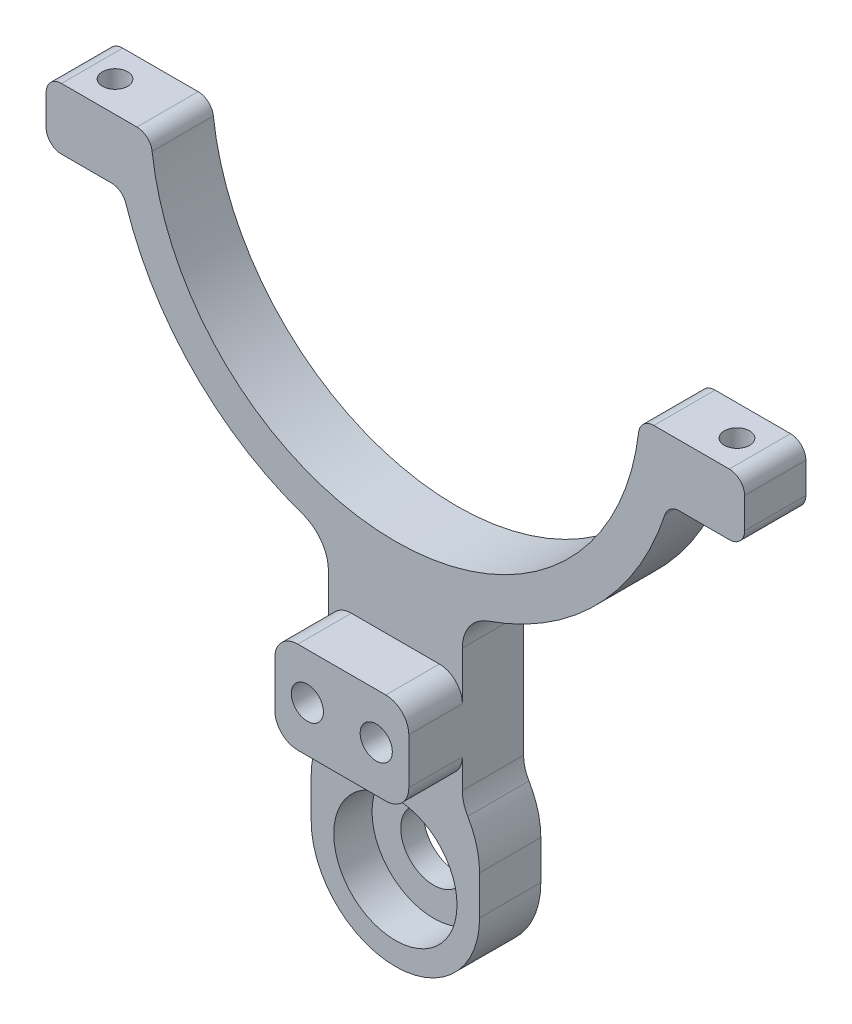
SolidWorks part; units mm, degrees
ref_plane "Front Plane" through (0, 0, 0) normal (0, 0, 1) x (1, 0, 0)
ref_plane "Top Plane" through (0, 0, 0) normal (0, 1, 0) x (1, 0, 0)
ref_plane "Right Plane" through (0, 0, 0) normal (1, 0, 0) x (0, 0, -1)
sketch "Sketch2" plane through (0, 0, 0) normal (0, 0, 1) x (1, 0, 0)
  circle A0 centre (0, 0) radius 31.7 construction
  dimension "D1" = 63.4
sketch "Sketch3" plane through (0, 0, 0) normal (0, 0, 1) x (1, 0, 0)
  line L0 (-31.9374, -2) -> (-45.623, -2)
  line L1 (31.9374, -2) -> (45.623, -2)
  line L7 (-11, -35.327) -> (-11, -80.1)
  line L8 (-11, -80.1) -> (11, -80.1)
  line L9 (11, -80.1) -> (11, -35.327)
  line L11 (35.623, -10) -> (45.623, -10)
  line L12 (45.623, -10) -> (45.623, -2)
  line L13 (-35.623, -10) -> (-45.623, -10)
  line L14 (-45.623, -10) -> (-45.623, -2)
  line L15 (40.623, -10) -> (40.623, -2) construction
  line L16 (37.623, -6) -> (43.623, -6) construction
  circle A1 centre (0, -69.1) radius 4 construction
  arc A2 (31.9374, -2) -> (-31.9374, -2) centre (0, 0) cw
  circle A3 centre (0, 0) radius 31.7 construction
  circle A7 centre (0, -69.1) radius 8.05
  arc A8 (11, -35.327) -> (35.623, -10) centre (0, 0) ccw
  arc A9 (-11, -35.327) -> (-35.623, -10) centre (0, 0) cw
  point P9 (0, -80.1)
  point P24 (40.623, -6)
  dimension "D1" = 0.3
  dimension "D3" = 37.4
  dimension "D4" = 8
  dimension "D5" = 16.1
  dimension "D7" = 5
  dimension "D2" = 48.4
  dimension "D6" = 22
  dimension "D8" = 8
  dimension "D9" = 6
  dimension "D10" = 2
  dimension "D11" = 2
  dimension "D12" = 2
extrude "Boss-Extrude1" add sketch "Sketch3" along normal blind 8
sketch "Sketch4" plane through (0, 0, 0) normal (0, 0, 1) x (1, 0, 0)
  circle A0 centre (0, -69.1) radius 8.05 construction
  circle A1 centre (0, -69.1) radius 8.05
  circle A2 centre (0, -69.1) radius 4.3
  dimension "D1" = 8.6
extrude "Boss-Extrude2" add sketch "Sketch4" along normal offset from surface (3 mm away) 5 up to face at (0, -26.2592, 8)
chamfer "Chamfer1" distance 3 angle 45 1 edges at (0, -80.1, 0)
fillet "Fillet1" radius 11 2 edges at (-11, -80.1, 5.5) (11, -80.1, 5.5)
sketch "Sketch5" plane through (0, -10, 0) normal (0, -1, 0) x (1, 0, 0)
  line L0 (37.623, 0) -> (43.623, 0) construction
  line L1 (37.623, 0) -> (43.623, 0) construction
  line L2 (40.623, 0) -> (40.623, 8) construction
  line L3 (45.623, 8) -> (31.9374, 8) construction
  line L4 (0, 0) -> (0, 8) construction
  line L5 (31.7, 0) -> (-31.7, 0) construction
  line L6 (31.9374, 8) -> (-31.9374, 8) construction
  circle A0 centre (40.623, 4) radius 1.65
  dimension "D1" = 3.3
extrude "Cut-Extrude1" cut sketch "Sketch5" against normal through all
sketch "Sketch6" plane through (0, -10, 0) normal (0, -1, 0) x (1, 0, 0)
  circle A0 centre (40.623, 4) radius 3
  dimension "D1" = 6
extrude "Cut-Extrude2" cut sketch "Sketch6" against normal blind 3
mirror "Mirror1" about plane through (0, 0, 0) normal (1, 0, 0) of "Cut-Extrude2", "Cut-Extrude1"
sketch "Sketch7" plane through (0, 0, 8) normal (0, 0, 1) x (1, 0, 0)
  line L0 (-4.5, -49) -> (4.5, -49) construction
  circle A0 centre (-4.5, -49) radius 2.1
  circle A1 centre (4.5, -49) radius 2.1
  point P4 (0, -49)
  dimension "D2" = 4.2
  dimension "D1" = 9
  dimension "D3" = 49
extrude "Cut-Extrude3" cut sketch "Sketch7" against normal blind 5
sketch "Sketch8" plane through (0, 0, 8) normal (0, 0, 1) x (1, 0, 0)
  circle A0 centre (4.5, -49) radius 2.1 construction
  circle A1 centre (-4.5, -49) radius 2.1 construction
  circle A2 centre (4.5, -49) radius 2.1 construction
  circle A3 centre (-4.5, -49) radius 2.1 construction
  circle A4 centre (4.5, -49) radius 1.65
  circle A5 centre (-4.5, -49) radius 1.65
  dimension "D1" = 3.3
extrude "Cut-Extrude4" cut sketch "Sketch8" against normal through all
sketch "Sketch9" plane through (0, 0, 8) normal (0, 0, 1) x (1, 0, 0)
  line L0 (-8.75, -35.9505) -> (-8.75, -57.3339)
  line L1 (8.75, -57.3339) -> (8.75, -35.9505)
  line L2 (-8.75, -43.6314) -> (8.75, -43.6314) construction
  line L3 (-11, -35.327) -> (-11, -69.1) construction
  line L4 (11, -69.1) -> (11, -35.327) construction
  line L5 (-11, -35.327) -> (-11, -64)
  line L6 (11, -35.327) -> (11, -64)
  arc A0 (-8.75, -35.9505) -> (-11, -35.327) centre (0, 0) cw
  arc A1 (8.75, -35.9505) -> (11, -35.327) centre (0, 0) ccw
  arc A2 (-35.623, -10) -> (-11, -35.327) centre (0, 0) ccw construction
  arc A3 (-8.75, -57.3339) -> (-11, -64) centre (0, -64) ccw
  arc A4 (8.75, -57.3339) -> (11, -64) centre (0, -64) cw
  point P6 (0, -43.6314)
  dimension "D1" = 17.5
  dimension "D2" = 64
extrude "Cut-Extrude5" cut sketch "Sketch9" against normal through all
fillet "Fillet2" radius 5 4 edges at (-8.75, -57.3339, 4) (8.75, -57.3339, 4) (8.75, -35.9505, 4) (-8.75, -35.9505, 4)
fillet "Fillet3" radius 2 8 edges at (-35.623, -10, 4) (-45.623, -2, 4) (-31.9374, -2, 4) (31.9374, -2, 4) (45.623, -2, 4) (45.623, -10, 4) (35.623, -10, 4) (-45.623, -10, 4)
sketch "Sketch10" plane through (0, 0, 8) normal (0, 0, 1) x (1, 0, 0)
  line L0 (-8.75, -55.8185) -> (-8.75, -39.6855) construction
  line L1 (-8.75, -43) -> (8.75, -43)
  line L2 (-8.75, -43) -> (-8.75, -55)
  line L3 (-8.75, -55) -> (8.75, -55)
  line L4 (8.75, -43) -> (8.75, -55)
  line L5 (-4.5, -49) -> (4.5, -49) construction
  line L6 (0, -43) -> (0, -55) construction
  line L7 (8.75, -39.6855) -> (8.75, -55.8185) construction
  circle A1 centre (4.5, -49) radius 2.1 construction
  circle A2 centre (-4.5, -49) radius 2.1 construction
  circle A3 centre (4.5, -49) radius 2.1
  circle A4 centre (-4.5, -49) radius 2.1
  point P14 (0, -49)
  dimension "D1" = 12
extrude "Boss-Extrude3" add sketch "Sketch10" along normal blind 7
fillet "Fillet4" radius 3 4 edges at (-8.75, -43, 11.5) (8.75, -43, 11.5) (8.75, -55, 11.5) (-8.75, -55, 11.5)
sketch "Sketch11" plane through (0, 0, 3) normal (0, 0, 1) x (1, 0, 0)
  circle A0 centre (4.5, -49) radius 2.1 construction
  circle A1 centre (-4.5, -49) radius 2.1 construction
  circle A2 centre (4.5, -49) radius 2.1
  circle A3 centre (-4.5, -49) radius 2.1
  circle A4 centre (4.5, -49) radius 1.65 construction
  circle A5 centre (-4.5, -49) radius 1.65 construction
  circle A6 centre (4.5, -49) radius 1.65
  circle A7 centre (-4.5, -49) radius 1.65
extrude "Boss-Extrude4" add sketch "Sketch11" along normal offset from surface (7 mm away) 5 up to face at (6.6, -49, 15)
